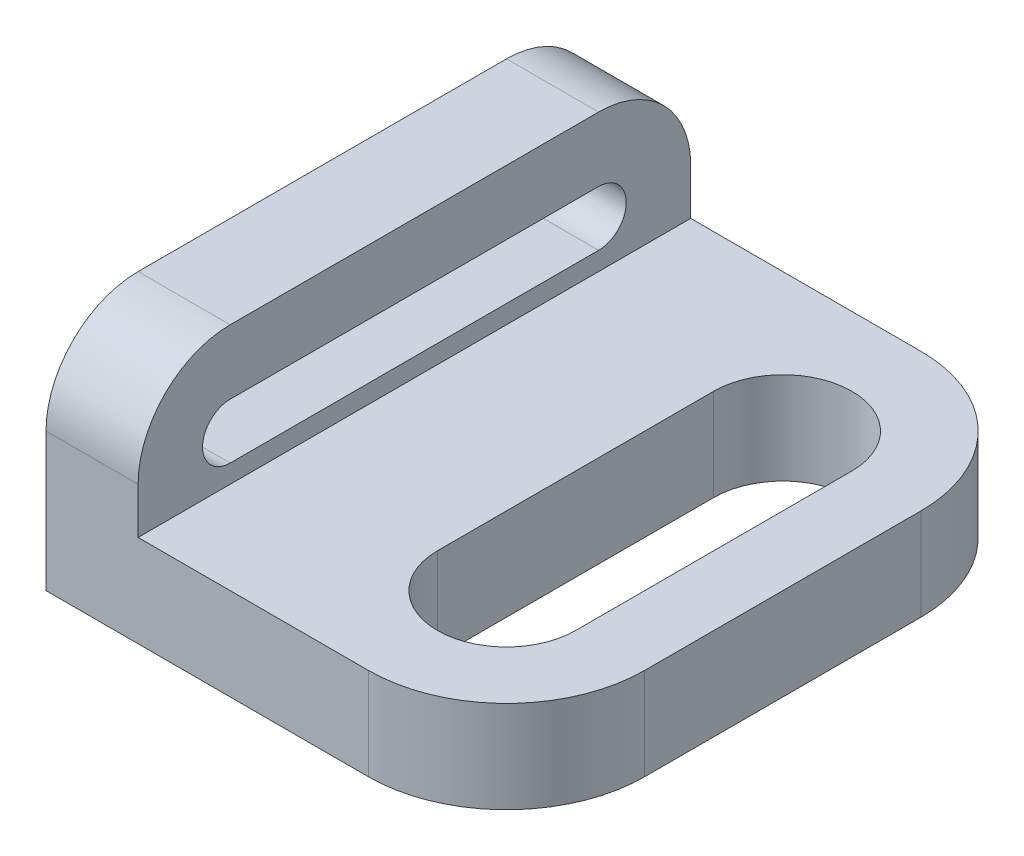
SolidWorks part; units mm, degrees
ref_plane "Front Plane" through (0, 0, 0) normal (0, 0, 1) x (1, 0, 0)
ref_plane "Top Plane" through (0, 0, 0) normal (0, 1, 0) x (1, 0, 0)
ref_plane "Right Plane" through (0, 0, 0) normal (1, 0, 0) x (0, 0, -1)
sketch "Sketch2" plane through (0, 0, 0) normal (0, 1, 0) x (1, 0, 0)
  line L0 (20, 120) -> (20, 0)
  line L1 (0, 0) -> (70, 0)
  line L2 (0, 0) -> (0, 120)
  line L3 (0, 120) -> (70, 120)
  line L4 (100, 30) -> (100, 90)
  line L5 (55, 90) -> (55, 30)
  line L6 (85, 90) -> (85, 30)
  arc A0 (85, 90) -> (55, 90) centre (70, 90) ccw
  arc A1 (55, 30) -> (85, 30) centre (70, 30) ccw
  arc A2 (100, 90) -> (70, 120) centre (70, 90) ccw
  arc A3 (70, 0) -> (100, 30) centre (70, 30) ccw
  dimension "D7" = 70
  dimension "D1" = 120
  dimension "D3" = 30
  dimension "D4" = 30
  dimension "D5" = 60
  dimension "D6" = 20
extrude "Boss-Extrude1" add sketch "Sketch2" along normal blind 20 contours L1 A3 L4 A2 L3 L0 A1 L5 A0 L6 region at (54.3444, 0, -60)
extrude "Boss-Extrude2" add sketch "Sketch2<3>" along normal blind 50 contours L3 L2 L1 L0 region at (10, 0, -60)
sketch "Sketch2<3>" plane through (0, 0, 0) normal (0, 1, 0) x (1, 0, 0) same geometry as "Sketch2"
fillet "Fillet1" radius 20 2 edges at (10, 50, -120) (10, 50, 0)
sketch "Sketch3" plane through (20, 0, 0) normal (1, 0, 0) x (0, 0, -1)
  line L0 (0, 0) -> (30, 0) construction
  line L1 (90, 0) -> (120, 0) construction
  line L3 (0, 30) -> (0, 20) construction
  line L6 (20, 24) -> (100, 24)
  line L7 (20, 36) -> (100, 36)
  arc A0 (20, 36) -> (20, 24) centre (20, 30) ccw
  arc A1 (100, 24) -> (100, 36) centre (100, 30) ccw
  dimension "D1" = 30
  dimension "D2" = 30
  dimension "D3" = 20
  dimension "D4" = 80
extrude "Cut-Extrude1" cut sketch "Sketch3" against normal blind 20
